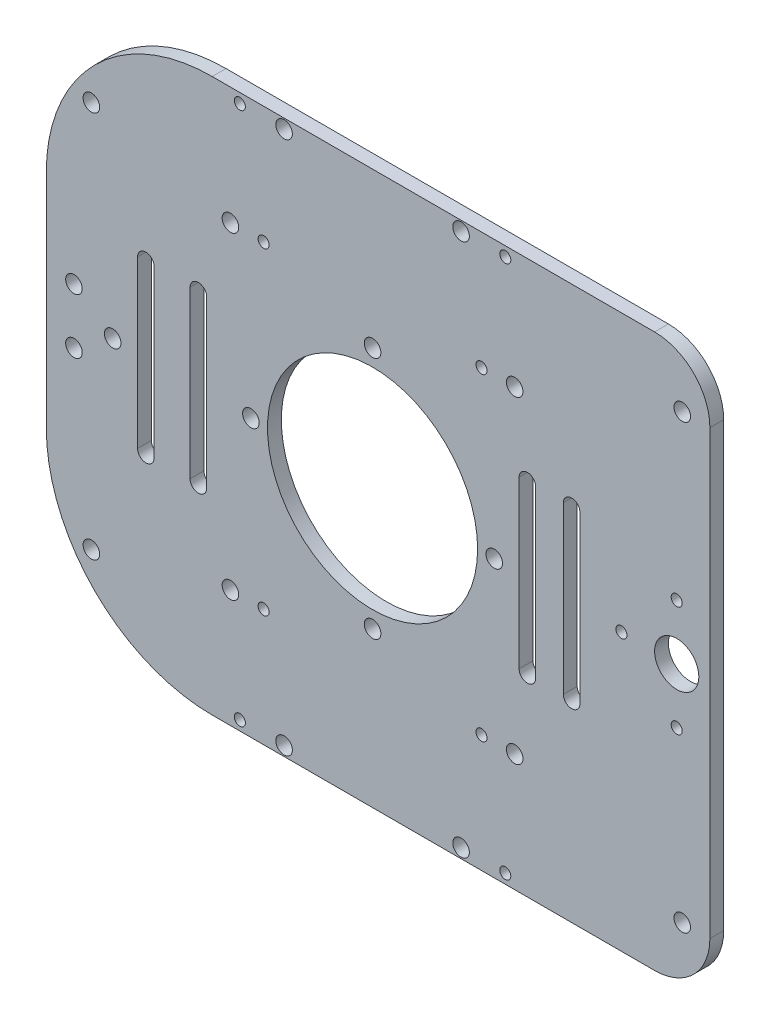
SolidWorks part; units mm, degrees
ref_plane "前视基准面" through (0, 0, 0) normal (0, 0, 1) x (1, 0, 0)
ref_plane "上视基准面" through (0, 0, 0) normal (0, 1, 0) x (1, 0, 0)
ref_plane "右视基准面" through (0, 0, 0) normal (1, 0, 0) x (0, 0, -1)
other "Configuration Table"
sketch "草图1" plane through (0, 0, 0) normal (0, 0, 1) x (1, 0, 0)
  line L0 (0, 0) -> (40.5006, 0) construction
  line L1 (-29, 50) -> (29, 50)
  line L2 (-29, 50) -> (-29, -50)
  line L3 (-29, -50) -> (29, -50)
  line L4 (29, 50) -> (29, -50)
  line L5 (-29, 50) -> (29, -50) construction
  line L6 (-29, -50) -> (29, 50) construction
  line L7 (0, 0) -> (0, 25.3918) construction
  line L8 (-16, 48.25) -> (-15.2, 48.25) construction
  line L9 (-15.2, 48.25) -> (-15.2, 41.2226) construction
  line L10 (15.2, 47.5) -> (15.2, 40.4726) construction
  circle A0 centre (-24, 48.25) radius 1
  circle A1 centre (-16, 48.25) radius 1.5
  circle A4 centre (16, 48.25) radius 1.5
  circle A5 centre (24, 48.25) radius 1
  circle A7 centre (-19.7, 28.75) radius 1
  circle A8 centre (-25.7, 28.75) radius 1.5
  circle A10 centre (19.7, 28.75) radius 1
  circle A11 centre (25.7, 28.75) radius 1.5
  circle A12 centre (25.7, -28.75) radius 1.5
  circle A13 centre (24, -48.25) radius 1
  circle A14 centre (16, -48.25) radius 1.5
  circle A15 centre (19.7, -28.75) radius 1
  circle A20 centre (-19.7, -28.75) radius 1
  circle A21 centre (-25.7, -28.75) radius 1.5
  circle A22 centre (-24, -48.25) radius 1
  circle A23 centre (-16, -48.25) radius 1.5
  point P0 (0, 0)
  dimension "D3" = 2
  dimension "D4" = 3
  dimension "D5" = 4.5
  dimension "D14" = 2
  dimension "D16" = 3
  dimension "D1" = 100
  dimension "D2" = 58
  dimension "D6" = 1.75
  dimension "D7" = 19.5
  dimension "D8" = 16
  dimension "D9" = 24
  dimension "D10" = 0.8
  dimension "D17" = 6
extrude "凸台-拉伸1" add sketch "草图1" along normal blind 2.5
sketch "草图2" plane through (0, 0, 2.5) normal (0, 0, 1) x (1, 0, 0)
  line L0 (29, 50) -> (-29, 50) construction
  line L1 (-59, 50) -> (61, 50)
  line L2 (-59, 50) -> (-59, -50)
  line L3 (-59, -50) -> (61, -50)
  line L4 (61, 50) -> (61, -50)
  line L5 (-29, -50) -> (29, -50) construction
  line L6 (-29, 50) -> (-29, -50) construction
  circle A0 centre (0, 0) radius 19
  circle A1 centre (0, 22) radius 1.5
  circle A2 centre (-22, 0) radius 1.5
  circle A3 centre (0, -22) radius 1.5
  circle A5 centre (22, 0) radius 1.5
  line M13 (29, -50) -> (29, 50)
  line M15 (-29, 50) -> (-29, -50)
  dimension "D3" = 38
  dimension "D4" = 3
  dimension "D1" = 30
  dimension "D2" = 120
  dimension "D5" = 22
  dimension "D6" = 22
  dimension "D7" = 22
  dimension "D8" = 22
extrude "切除-拉伸1" cut sketch "草图2" against normal blind 10 contours A3 | A2 | A1 | A0 | A5 region at (0, 0, 2.5) region at (0, 22, 2.5) region at (-22, 0, 2.5) region at (0, -22, 2.5) region at (22, 0, 2.5)
extrude "凸台-拉伸2" add sketch "草图2<3>" against normal blind 2.5 contours L2 L3 L1 M15 | L4 L1 L3 M13 region at (-44, 0, 2.5) region at (45, 0, 2.5)
sketch "草图2<3>" plane through (0, 0, 2.5) normal (0, 0, 1) x (1, 0, 0) same geometry as "草图2"
fillet "圆角1" radius 30 2 edges at (-59, 50, 1.25) (-59, -50, 1.25)
fillet "圆角2" radius 10 2 edges at (61, 50, 1.25) (61, -50, 1.25)
sketch "草图4" plane through (0, 0, 2.5) normal (0, 0, 1) x (1, 0, 0)
  line L0 (-59, 20) -> (-59, -20) construction
  line L1 (-41, -15) -> (-41, 15) construction
  line L2 (-42.5, -15) -> (-42.5, 15)
  line L3 (-39.5, -15) -> (-39.5, 15)
  line L4 (-56.2995, 0) -> (0, 0) construction
  line L5 (-31.5, -15) -> (-31.5, 15) construction
  line L6 (-33, -15) -> (-33, 15)
  line L7 (-30, -15) -> (-30, 15)
  line L11 (28, -15) -> (28, 15) construction
  line L12 (26.5, -15) -> (26.5, 15)
  line L13 (29.5, -15) -> (29.5, 15)
  line L14 (36, -15) -> (36, 15) construction
  line L15 (34.5, -15) -> (34.5, 15)
  line L16 (37.5, -15) -> (37.5, 15)
  line L20 (51, 50) -> (-29, 50) construction
  line L21 (61, 40) -> (61, -40) construction
  circle A0 centre (55, 0) radius 4
  circle A1 centre (55, 10) radius 1
  circle A2 centre (55, -10) radius 1
  circle A3 centre (45, 0) radius 1
  circle A4 centre (-54, 5) radius 1.5
  circle A5 centre (-54, -5) radius 1.5
  arc A6 (61, 40) -> (51, 50) centre (51, 40) ccw construction
  arc A7 (-42.5, -15) -> (-39.5, -15) centre (-41, -15) ccw
  arc A8 (-39.5, 15) -> (-42.5, 15) centre (-41, 15) ccw
  arc A9 (-33, -15) -> (-30, -15) centre (-31.5, -15) ccw
  arc A10 (-30, 15) -> (-33, 15) centre (-31.5, 15) ccw
  arc A13 (26.5, -15) -> (29.5, -15) centre (28, -15) ccw
  arc A14 (29.5, 15) -> (26.5, 15) centre (28, 15) ccw
  arc A15 (34.5, -15) -> (37.5, -15) centre (36, -15) ccw
  arc A16 (37.5, 15) -> (34.5, 15) centre (36, 15) ccw
  circle A19 centre (-50.8461, 35) radius 1.5
  circle A20 centre (56, -40) radius 1.5
  arc A21 (-29, 50) -> (-59, 20) centre (-29, 20) ccw construction
  circle A22 centre (-50.8461, -35) radius 1.5
  circle A23 centre (56, 40) radius 1.5
  circle A24 centre (-47, 0) radius 1.5
  point P15 (-41, 0)
  point P28 (-31.5, 0)
  point P41 (28, 0)
  point P47 (36, 0)
  dimension "D1" = 8
  dimension "D3" = 2
  dimension "D4" = 2
  dimension "D5" = 2
  dimension "D9" = 3
  dimension "D10" = 3
  dimension "D13" = 5
  dimension "D24" = 3
  dimension "D25" = 2
  dimension "D27" = 3
  dimension "D28" = 5
  dimension "D30" = 3
  dimension "D2" = 55
  dimension "D6" = 10
  dimension "D7" = 10
  dimension "D8" = 10
  dimension "D11" = 10
  dimension "D12" = 5
  dimension "D14" = 3
  dimension "D15" = 18
  dimension "D16" = 30
  dimension "D18" = 8
  dimension "D19" = 28
  dimension "D20" = 3
  dimension "D21" = 30
  dimension "D23" = 8
  dimension "D26" = 15
  dimension "D29" = 5
  dimension "D31" = 12
  dimension "D17" = 2
  dimension "D22" = 2
extrude "切除-拉伸3" cut sketch "草图4" against normal blind 10
